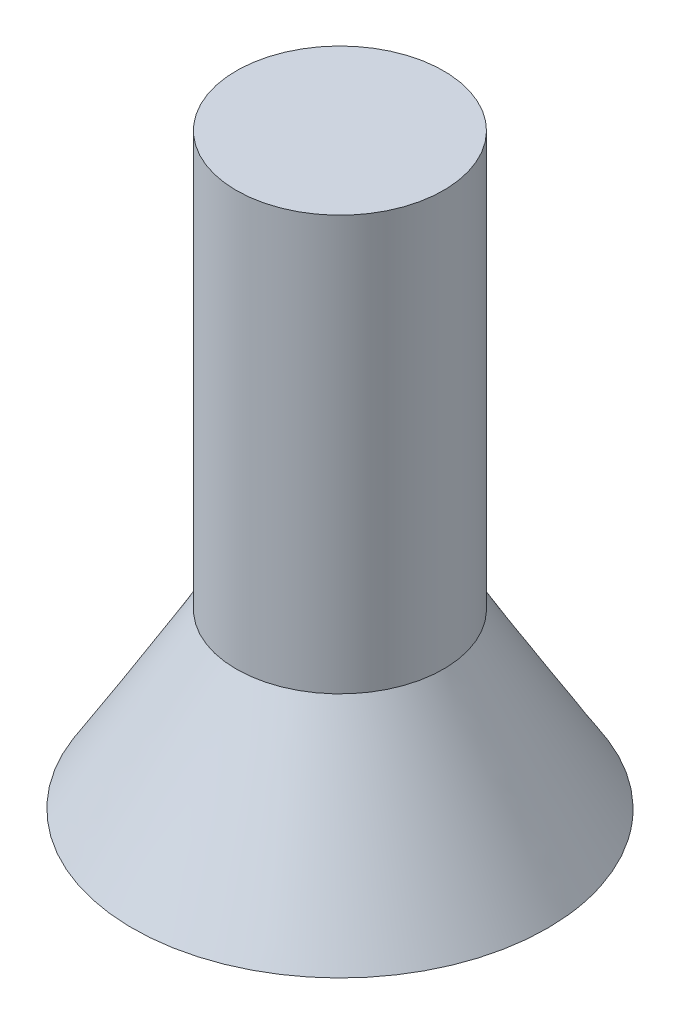
SolidWorks part; units mm, degrees
ref_plane "前视基准面" through (0, 0, 0) normal (0, 0, 1) x (1, 0, 0)
ref_plane "上视基准面" through (0, 0, 0) normal (0, 1, 0) x (1, 0, 0)
ref_plane "右视基准面" through (0, 0, 0) normal (1, 0, 0) x (0, 0, -1)
other "Configuration Table"
sketch "草图1" plane through (0, 0, 0) normal (0, 1, 0) x (1, 0, 0)
  circle A0 centre (0, 0) radius 3
  dimension "D1" = 6
ref_plane "基准面1" through (0, 2.5, 0) normal (0, 1, 0) x (1, 0, 0)
sketch "草图2" plane through (0, 2.5, 0) normal (0, 1, 0) x (1, 0, 0)
  circle A0 centre (0, 0) radius 1.5
  dimension "D1" = 3
loft "放样1" add profiles "草图1", "草图2" connector at (-2.6966, 0, 1.3147) connector at (-1.4639, 2.5, 0.3272)
sketch "草图3" plane through (0, 2.5, 0) normal (0, 1, 0) x (1, 0, 0)
  circle A1 centre (0, 0) radius 1.5
  circle A2 centre (0, 0) radius 1.5
  dimension "D1" = 0
extrude "凸台-拉伸1" add sketch "草图3" along normal blind 6
sketch "草图4" plane through (0, 0, 0) normal (0, -1, 0) x (1, 0, 0)
  line L1 (0.5774, 1) -> (-0.5774, 1)
  line L2 (-0.5774, 1) -> (-1.1547, 0)
  line L3 (-1.1547, 0) -> (-0.5774, -1)
  line L4 (-0.5774, -1) -> (0.5774, -1)
  line L5 (0.5774, -1) -> (1.1547, 0)
  line L6 (1.1547, 0) -> (0.5774, 1)
  circle A0 centre (0, 0) radius 1 construction
  dimension "D1" = 2
extrude "切除-拉伸1" cut sketch "草图4" against normal blind 0.5
equation "\"0。5\"=10"
